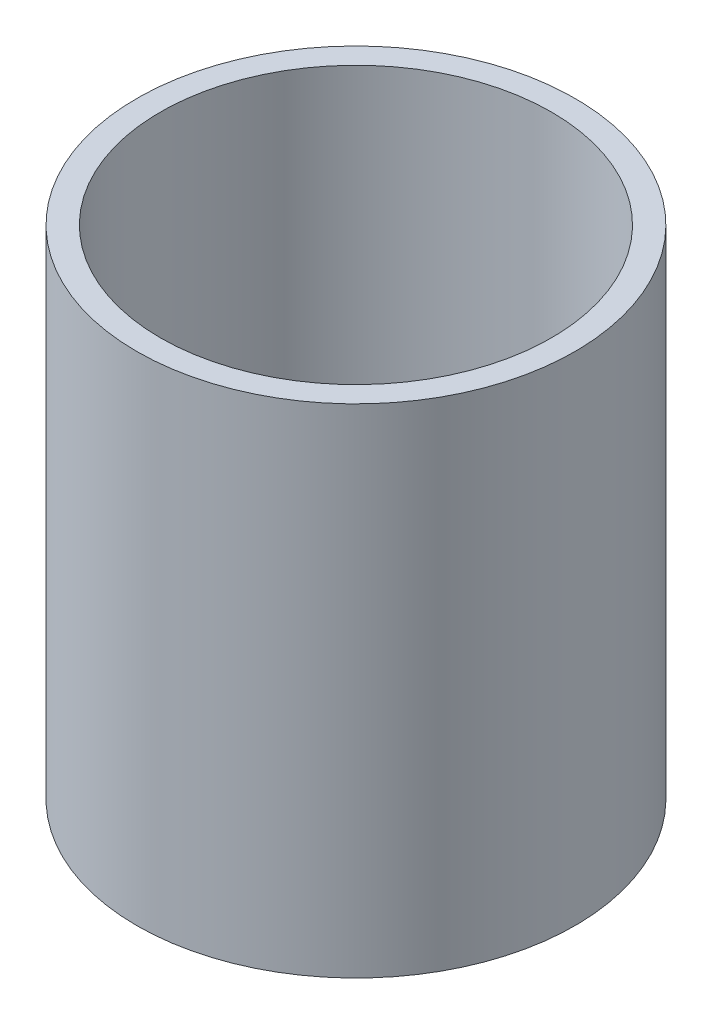
SolidWorks part; units mm, degrees
ref_plane "Front Plane" through (0, 0, 0) normal (0, 0, 1) x (1, 0, 0)
ref_plane "Top Plane" through (0, 0, 0) normal (0, 1, 0) x (1, 0, 0)
ref_plane "Right Plane" through (0, 0, 0) normal (1, 0, 0) x (0, 0, -1)
sketch "Sketch1" plane through (0, 0, 0) normal (0, 1, 0) x (1, 0, 0)
  circle A0 centre (0, 0) radius 50
  dimension "SLEEVE_OD" = 100
extrude "Boss-Extrude1" add sketch "Sketch1" along normal blind 113.4424
sketch "Sketch2" plane through (0, 0, 0) normal (0, 1, 0) x (1, 0, 0)
  circle A0 centre (0, 0) radius 44.6193
  dimension "BORE_D" = 89.2386
extrude "Cut-Extrude1" cut sketch "Sketch2" along normal through all
chamfer "Chamfer1" distance 3.8966 angle 45 rebuild error yes
